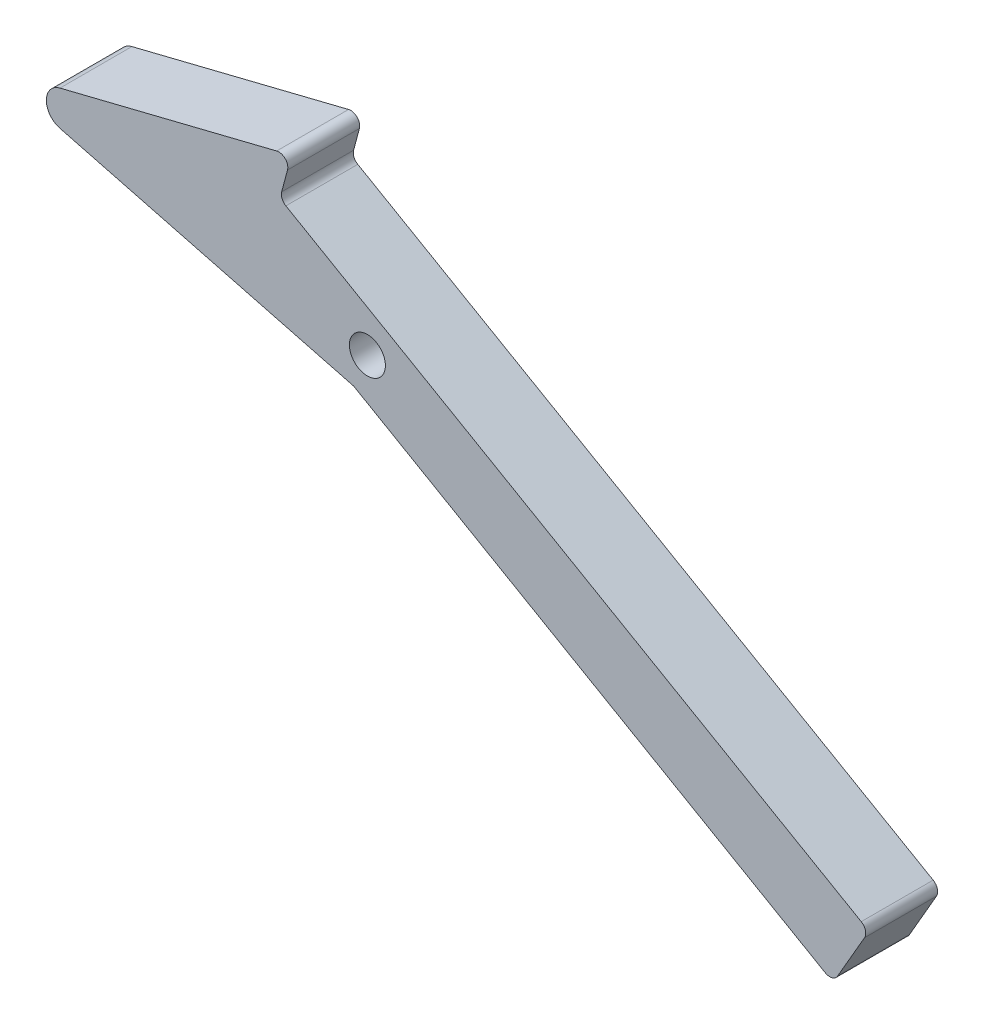
SolidWorks part; units mm, degrees
ref_plane "Front Plane" through (0, 0, 0) normal (0, 0, 1) x (1, 0, 0)
ref_plane "Top Plane" through (0, 0, 0) normal (0, 1, 0) x (1, 0, 0)
ref_plane "Right Plane" through (0, 0, 0) normal (1, 0, 0) x (0, 0, -1)
sketch "Sketch1" plane through (0, 0, 0) normal (0, 0, 1) x (1, 0, 0)
  line L13 (0.2988, 3.4937) -> (-7.7281, 8.128)
  line L22 (-7.7281, 8.128) -> (-6.7072, 11.938)
  line L23 (-6.7072, 11.938) -> (-27.1452, 6.858)
  line L24 (-7.7281, 8.128) -> (-7.7281, 3.2691) construction
  line L26 (-27.1617, 3.781) -> (-1.2151, -2.9646)
  line L27 (0.2988, 3.4937) -> (44.2929, -21.9063)
  line L28 (44.2929, -21.9063) -> (41.1179, -27.4056)
  line L29 (41.1179, -27.4056) -> (-1.2151, -2.9646)
  arc A0 (-27.1452, 6.858) -> (-27.1617, 3.781) centre (-26.7623, 5.3174) ccw
  circle A1 centre (0, 0) radius 3.175
  circle A2 centre (0, 0) radius 1.5875
  point P5 (-18.242, 2.0491)
  point P9 (-26.7145, 6.7271)
  dimension "D5" = 6.35
  dimension "D1" = 15
  dimension "D8" = 6.35
  dimension "D9" = 1.5875
  dimension "D10" = 3.175
  dimension "D2" = 60
  dimension "D3" = 3.81
  dimension "D4" = 120
  dimension "D6" = 50.8
  dimension "D7" = 5.08
  dimension "D11" = 8.128
extrude "Boss-Extrude1" add sketch "Sketch1" along normal blind 3.175 and the other way blind 3.175 contours A1 L29 L28 L27 L13 L22 L23 A0 L26 | A1 region at (2.6719, 1.5426, 0) region at (7.7976, -5.6972, 0)
fillet "Fillet1" radius 0.7937 4 edges at (44.2929, -21.9063, 0) (41.1179, -27.4056, 0) (-7.7281, 8.128, 0) (-6.7072, 11.938, 0)
